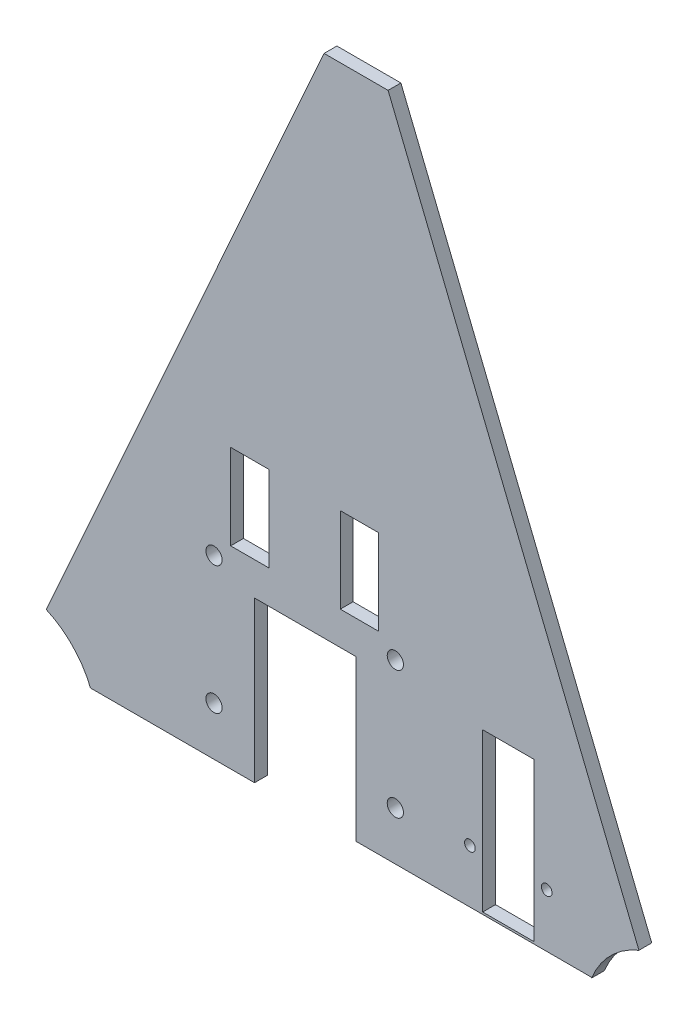
SolidWorks part; units mm, degrees
ref_plane "Front Plane" through (0, 0, 0) normal (0, 0, 1) x (1, 0, 0)
ref_plane "Top Plane" through (0, 0, 0) normal (0, 1, 0) x (1, 0, 0)
ref_plane "Right Plane" through (0, 0, 0) normal (1, 0, 0) x (0, 0, -1)
sketch "Sketch2" plane through (0, 0, 0) normal (0, 0, 1) x (1, 0, 0)
  line L0 (-189.7401, 245.3834) -> (-375.9085, -170.4146)
  line L1 (-375.9085, -170.4146) -> (16.7755, -170.4146)
  line L2 (16.7755, -170.4146) -> (-151.6401, 245.3834)
  line L4 (-189.7401, 245.3834) -> (-151.6401, 245.3834)
  dimension "D1" = 415.798
  dimension "D2" = 415.798
  dimension "D3" = 67.95
  dimension "D4" = 38.1
  dimension "D5" = 392.684
extrude "Boss-Extrude1" add sketch "Sketch2" along normal blind 7.62 contours L0 L1 L2 L4
sketch "Sketch5" plane through (0, 0, 0) normal (0, 0, -1) x (-1, 0, 0)
  circle A0 centre (375.9085, -170.4146) radius 15.875
  dimension "D1" = 31.75
extrude "Cut-Extrude2" cut sketch "Sketch5" against normal blind 50.8
sketch "Sketch6" plane through (0, 0, 0) normal (0, 0, -1) x (-1, 0, 0)
  circle A0 centre (-16.7755, -170.4146) radius 15.875
  dimension "D1" = 31.75
extrude "Cut-Extrude3" cut sketch "Sketch6" against normal blind 50.8 contours A0
ref_plane "Plane1" through (-360.0335, -170.4146, 0) normal (1, 0, 0) x (0, 0, -1)
sketch "Sketch8" plane through (0, 0, 0) normal (0, 0, -1) x (-1, 0, 0)
  line L0 (254.9716, -43.4146) -> (147.0216, -43.4146) construction
  line L1 (360.0335, -170.4146) -> (-0.9005, -170.4146) construction
  line L2 (254.9716, -170.4146) -> (254.9716, 97.7332) construction
  line L3 (254.9716, -43.4146) -> (254.9716, -170.4146) construction
  line L4 (147.0216, -43.4146) -> (147.0216, -170.4146) construction
  line L5 (147.0216, -170.4146) -> (183.5239, -170.4146) construction
  line L6 (183.5239, -170.4146) -> (183.5239, -56.1146) construction
  line L7 (170.6901, 245.3834) -> (179.5665, -170.4146) construction
  line L8 (189.7401, 245.3834) -> (151.6401, 245.3834) construction
  line L9 (183.5239, -56.1146) -> (218.4489, -56.1146) construction
  line L10 (218.4489, -56.1146) -> (218.4489, -170.4146) construction
  line L11 (218.4489, -170.4146) -> (218.4489, -56.1146)
  line L12 (218.4489, -56.1146) -> (183.5239, -56.1146)
  line L13 (183.5239, -56.1146) -> (183.5239, -170.4146)
  line L14 (153.8492, -170.4146) -> (153.8492, -48.647) construction
  dimension "D1" = 268.1478
  dimension "D2" = 107.95
  dimension "D3" = 127
  dimension "D4" = 36.5023
  dimension "D5" = 114.3
  dimension "D6" = 34.925
  dimension "D7" = 121.7676
extrude "Cut-Extrude4" cut sketch "Sketch8" against normal blind 7.62 and the other way through all contours L11 L12 L13
sketch "Sketch9" plane through (0, 0, 0) normal (0, 0, -1) x (-1, 0, 0)
  line L0 (152.1549, -122.4086) -> (183.5239, -122.4086) construction
  line L1 (183.5239, -170.4146) -> (183.5239, -56.1146) construction
  line L2 (147.3289, -127.2346) -> (147.3289, -170.4146) construction
  line L3 (183.5239, -170.4146) -> (-0.9005, -170.4146) construction
  line L4 (250.4529, -122.4086) -> (218.4489, -122.4086) construction
  line L5 (218.4489, -56.1146) -> (218.4489, -170.4146) construction
  line L6 (255.2789, -127.2346) -> (255.2789, -170.4146) construction
  line L7 (360.0335, -170.4146) -> (218.4489, -170.4146) construction
  circle A0 centre (147.3289, -122.4086) radius 4.826
  circle A1 centre (255.2789, -122.4086) radius 4.826
  dimension "D3" = 9.652
  dimension "D6" = 9.652
  dimension "D1" = 31.369
  dimension "D2" = 43.18
  dimension "D4" = 32.004
  dimension "D5" = 43.18
sketch "Sketch10" plane through (0, 0, 0) normal (0, 0, -1) x (-1, 0, 0)
  line L0 (218.4489, -110.7541) -> (349.1963, -110.7541) construction
  line L1 (218.4489, -56.1146) -> (218.4489, -170.4146) construction
  line L2 (189.7401, 245.3834) -> (369.4213, -155.9256) construction
  line L3 (7.3895, -110.7541) -> (138.1995, -110.7541) construction
  line L4 (-10.8158, -155.7008) -> (151.6401, 245.3834) construction
  line L5 (64.8263, -170.4146) -> (64.8263, -56.1146) construction
  line L8 (183.5239, -170.4146) -> (-0.9005, -170.4146) construction
  line L9 (64.8263, -56.1146) -> (95.3063, -56.1146) construction
  line L11 (95.3063, -56.1146) -> (95.3063, -170.4146) construction
  line L12 (64.8263, -170.4146) -> (64.8263, -56.1146)
  line L13 (64.8263, -56.1146) -> (95.3063, -56.1146)
  line L14 (95.3063, -56.1146) -> (95.3063, -170.4146)
  line L15 (64.8263, -170.4146) -> (95.3063, -170.4146)
  dimension "D1" = 130.7473
  dimension "D2" = 130.81
  dimension "D3" = 114.3
  dimension "D4" = 30.48
extrude "Cut-Extrude6" cut sketch "Sketch9" against normal up to next
extrude "Cut-Extrude12" cut sketch "Sketch10" against normal blind 25.4 contours L13 L14 L15 L12
sketch "Sketch13" plane through (0, 0, 0) normal (0, 0, -1) x (-1, 0, 0)
  line L0 (80.0663, -56.1146) -> (80.0663, -50.7806) construction
  line L1 (64.8263, -56.1146) -> (95.3063, -56.1146) construction
  line L2 (80.0663, -50.7806) -> (80.0663, -45.9546) construction
  circle A0 centre (80.0663, -45.9546) radius 4.826
  dimension "D3" = 9.652
  dimension "D1" = 5.334
  dimension "D2" = 4.826
sketch "Sketch14" plane through (0, 0, 0) normal (0, 0, -1) x (-1, 0, 0)
  circle A0 centre (-16.7755, -170.4146) radius 50.8
  dimension "D1" = 101.6
extrude "Cut-Extrude14" cut sketch "Sketch14" against normal up to next
sketch "Sketch15" plane through (0, 0, 0) normal (0, 0, -1) x (-1, 0, 0)
  circle A0 centre (375.9085, -170.4146) radius 50.8
  dimension "D1" = 101.6
extrude "Cut-Extrude15" cut sketch "Sketch15" against normal up to next
sketch "Sketch16" plane through (0, 0, 0) normal (0, 0, -1) x (-1, 0, 0)
  line L0 (95.3063, -56.1146) -> (95.3063, -170.4146) construction
  line L1 (95.3063, -150.0946) -> (64.8263, -150.0946)
  line L2 (95.3063, -150.0946) -> (95.3063, -170.4146)
  line L3 (95.3063, -170.4146) -> (64.8263, -170.4146)
  line L4 (64.8263, -150.0946) -> (64.8263, -170.4146)
  dimension "D1" = 20.32
extrude "Boss-Extrude2" add sketch "Sketch16" against normal blind 7.62
sketch "Sketch17" plane through (0, 0, 0) normal (0, 0, -1) x (-1, 0, 0)
  line L0 (64.8263, -150.0946) -> (64.8263, -125.9646) construction
  line L1 (64.8263, -150.0946) -> (64.8263, -56.1146) construction
  line L2 (64.8263, -125.9646) -> (64.8263, -113.2646) construction
  line L3 (64.8263, -113.2646) -> (49.5863, -113.2646) construction
  line L4 (49.5863, -113.2646) -> (49.5863, -125.9646) construction
  line L5 (49.5863, -125.9646) -> (64.8263, -125.9646) construction
  line L6 (49.5863, -119.6146) -> (64.8263, -119.6146) construction
  line L7 (95.3063, -113.2646) -> (110.5463, -113.2646) construction
  line L8 (95.3063, -56.1146) -> (95.3063, -150.0946) construction
  line L9 (110.5463, -113.2646) -> (110.5463, -125.9646) construction
  line L10 (110.5463, -125.9646) -> (95.3063, -125.9646) construction
  line L11 (110.5463, -119.6146) -> (95.3063, -119.6146) construction
  circle A0 centre (57.2063, -119.6146) radius 3.175
  circle A3 centre (102.9263, -119.6146) radius 3.175
  dimension "D4" = 6.35
  dimension "D7" = 6.35
  dimension "D1" = 24.13
  dimension "D2" = 12.7
  dimension "D3" = 15.24
  dimension "D5" = 15.24
  dimension "D6" = 12.7
extrude "Cut-Extrude16" cut sketch "Sketch17" against normal up to next
sketch "Sketch18" plane through (0, 0, 0) normal (0, 0, -1) x (-1, 0, 0)
  line L5 (30.4451, -170.4146) -> (331.0546, -170.4146)
  line L6 (30.4451, -170.4146) -> (30.4451, -151.3646)
  line L7 (30.4451, -151.3646) -> (331.0546, -151.3646)
  line L8 (331.0546, -170.4146) -> (331.0546, -151.3646)
  dimension "D1" = 19.05
extrude "Cut-Extrude17" cut sketch "Sketch18" against normal up to next (7.62 mm away) contours L7 L8 L5 L6
sketch "Sketch19" plane through (0, 0, 0) normal (0, 0, -1) x (-1, 0, 0)
  line L0 (255.2789, -122.4086) -> (255.2789, -46.2086) construction
  line L1 (147.3289, -122.4086) -> (147.3289, -46.2086) construction
  circle A0 centre (255.2789, -46.2086) radius 4.826
  circle A1 centre (147.3289, -46.2086) radius 4.826
  dimension "D3" = 9.652
  dimension "D4" = 9.652
  dimension "D1" = 76.2
  dimension "D2" = 76.2
extrude "Cut-Extrude18" cut sketch "Sketch19" against normal up to next
sketch "Sketch20" plane through (0, 0, 0) normal (0, 0, -1) x (-1, 0, 0)
  line L0 (152.1549, -46.2086) -> (253.7549, -46.2086) construction
  line L5 (253.7549, -46.2086) -> (253.7549, -28.5286) construction
  line L6 (147.3289, -46.2086) -> (147.3289, 23.5628) construction
  line L7 (157.2349, 14.4658) -> (180.0949, 14.4658)
  line L8 (157.2349, 14.4658) -> (157.2349, -36.3342)
  line L9 (157.2349, -36.3342) -> (180.0949, -36.3342)
  line L10 (180.0949, 14.4658) -> (180.0949, -36.3342)
  line L11 (157.2349, -10.9342) -> (147.3289, -10.9342) construction
  line L12 (255.2789, -46.2086) -> (255.2789, 23.5628) construction
  line L13 (222.5129, 14.4658) -> (245.3729, 14.4658)
  line L14 (222.5129, 14.4658) -> (222.5129, -36.3342)
  line L15 (222.5129, -36.3342) -> (245.3729, -36.3342)
  line L16 (245.3729, 14.4658) -> (245.3729, -36.3342)
  line L17 (245.3729, -10.9342) -> (255.2789, -10.9342) construction
  line L18 (168.6649, -36.3342) -> (168.6649, -46.2086) construction
  line L19 (233.9429, -36.3342) -> (233.9429, -46.2086) construction
  circle A0 centre (147.3289, -46.2086) radius 4.826 construction
  dimension "D1" = 22.86
  dimension "D2" = 50.8
  dimension "D3" = 101.6
  dimension "D4" = 9.906
  dimension "D5" = 22.86
  dimension "D6" = 50.8
  dimension "D7" = 9.906
  dimension "D8" = 9.8744
extrude "Cut-Extrude19" cut sketch "Sketch20" against normal up to next contours L14 L15 L16 L13 | L10 L9 L8 L7
sketch "Sketch21" plane through (0, 0, 0) normal (0, 0, -1) x (-1, 0, 0)
  line L1 (218.4489, -151.3646) -> (231.1489, -151.3646)
  line L2 (218.4489, -151.3646) -> (218.4489, -56.1146)
  line L3 (218.4489, -56.1146) -> (231.1489, -56.1146)
  line L4 (231.1489, -151.3646) -> (231.1489, -56.1146)
  line L5 (183.5239, -151.3646) -> (170.8239, -151.3646)
  line L6 (183.5239, -151.3646) -> (183.5239, -56.1146)
  line L7 (183.5239, -56.1146) -> (170.8239, -56.1146)
  line L8 (170.8239, -151.3646) -> (170.8239, -56.1146)
  point P10 (0, 0)
  point P11 (0, 0)
  dimension "D1" = 12.7
  dimension "D2" = 95.25
  dimension "D3" = 12.7
  dimension "D4" = 95.25
extrude "Cut-Extrude20" cut sketch "Sketch21" against normal up to next contours L4 L3 L2 L1 | L8 L7 L6 L5
